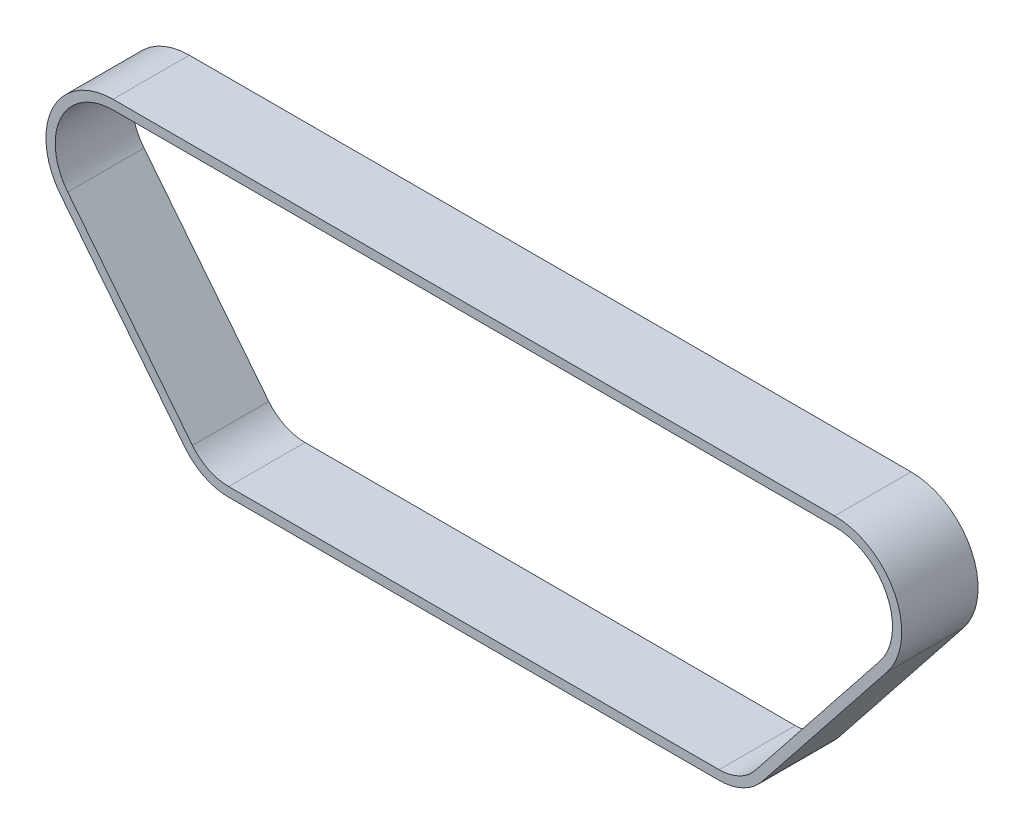
SolidWorks part; units mm, degrees
ref_plane "Front Plane" through (0, 0, 0) normal (0, 0, 1) x (1, 0, 0)
ref_plane "Top Plane" through (0, 0, 0) normal (0, 1, 0) x (1, 0, 0)
ref_plane "Right Plane" through (0, 0, 0) normal (1, 0, 0) x (0, 0, -1)
sketch "Sketch1" plane through (0, 0, 0) normal (0, 0, 1) x (1, 0, 0)
  line L0 (-156, 12.5) -> (0, 12.5)
  line L2 (-17.169, -41.719) -> (9.7887, -7.7737)
  line L4 (-165.7887, -7.7737) -> (-138.831, -41.719)
  line L6 (-131, -45.5) -> (-25, -45.5)
  line L8 (-156, 14.5) -> (0, 14.5)
  line L9 (-15.6028, -42.9628) -> (11.3549, -9.0175)
  line L10 (-131, -47.5) -> (-25, -47.5)
  line L11 (-167.3549, -9.0175) -> (-140.3972, -42.9628)
  circle A0 centre (-131, -35.5) radius 10 construction
  arc A2 (-138.831, -41.719) -> (-131, -45.5) centre (-131, -35.5) ccw
  circle A4 centre (-156, 0) radius 12.5 construction
  arc A6 (11.3549, -9.0175) -> (0, 14.5) centre (0, 0) ccw
  arc A12 (-156, 12.5) -> (-165.7887, -7.7737) centre (-156, 0) ccw
  arc A13 (-25, -47.5) -> (-15.6028, -42.9628) centre (-25, -35.5) ccw
  circle A15 centre (0, 0) radius 12.5 construction
  arc A16 (9.7887, -7.7737) -> (0, 12.5) centre (0, 0) ccw
  arc A19 (-140.3972, -42.9628) -> (-131, -47.5) centre (-131, -35.5) ccw
  arc A20 (-156, 14.5) -> (-167.3549, -9.0175) centre (-156, 0) ccw
  arc A21 (-25, -45.5) -> (-17.169, -41.719) centre (-25, -35.5) ccw construction
  circle A22 centre (-25, -35.5) radius 10 construction
  arc A23 (-25, -45.5) -> (-17.169, -41.719) centre (-25, -35.5) ccw
  point P29 (0, 0)
  point P30 (-25, -45.5)
  dimension "D1" = 2
extrude "Boss-Extrude1" add sketch "Sketch1" along normal mid plane 16.5
